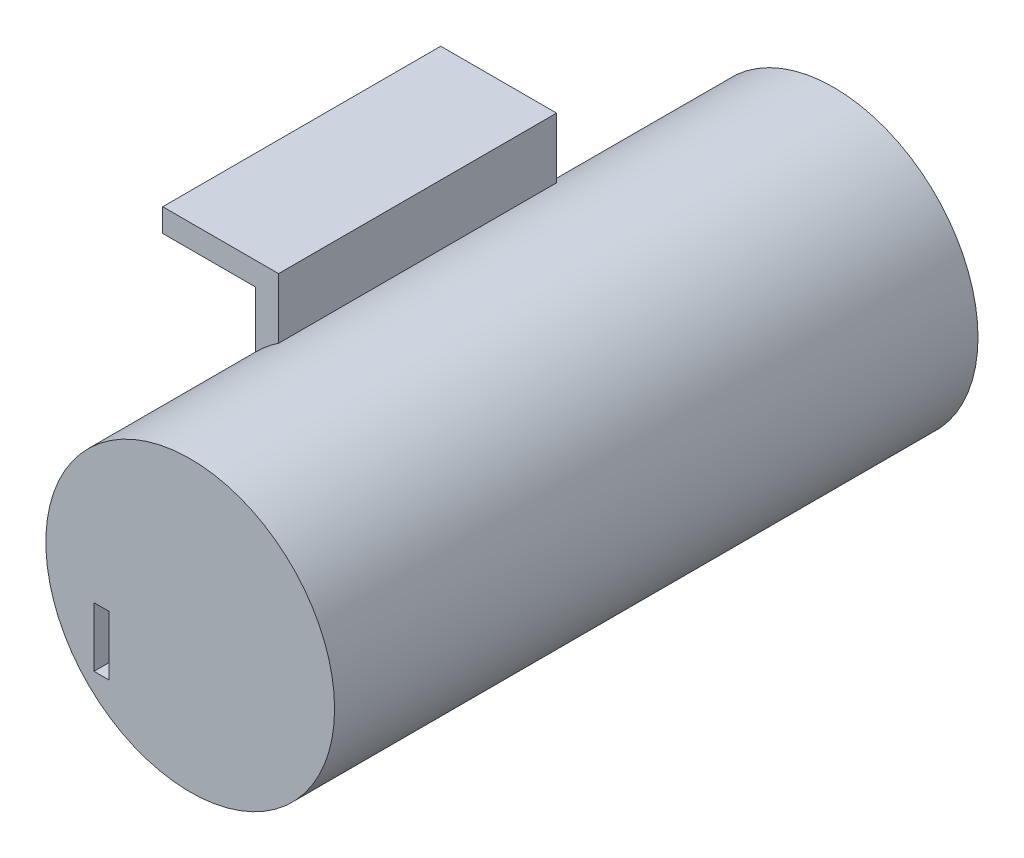
SolidWorks part; units mm, degrees
ref_plane "Front" through (0, 0, 0) normal (0, 0, 1) x (1, 0, 0)
ref_plane "Top" through (0, 0, 0) normal (0, 1, 0) x (1, 0, 0)
ref_plane "Right" through (0, 0, 0) normal (1, 0, 0) x (0, 0, -1)
sketch "Sketch1" plane through (0, 0, 0) normal (0, 0, 1) x (1, 0, 0)
  line L1 (-9.812, 11.8757) -> (-6.637, 11.8757)
  line L2 (-9.812, 11.8757) -> (-9.812, 0.8757)
  line L3 (-9.812, 0.8757) -> (-6.637, 0.8757)
  line L4 (-6.637, 11.8757) -> (-6.637, 0.8757)
  line L5 (-9.812, 8.7007) -> (-22.512, 8.7007)
  line L6 (-9.812, 8.7007) -> (-9.812, 11.8757)
  line L7 (-9.812, 11.8757) -> (-22.512, 11.8757)
  line L8 (-22.512, 8.7007) -> (-22.512, 11.8757)
  dimension "D1" = 11
  dimension "D2" = 3.175
  dimension "D3" = 3.175
  dimension "D4" = 12.7
extrude "Boss-Extrude1" add sketch "Sketch1" along normal blind 38.1 contours L8 L5 L2 L7 | L4 L1 L2 L3 region at (-8.2245, 6.3757, 0) region at (-16.162, 10.2882, 0)
sketch "Sketch2" plane through (0, 0, 0) normal (0, 0, -1) x (-1, 0, 0)
  circle A0 centre (-4.3298, -12.862) radius 19.7846
  circle A1 centre (-4.3298, -12.862) radius 18.4
extrude "Boss-Extrude2" add sketch "Sketch2" against normal blind 58 and the other way blind 27
sketch "Sketch3" plane through (0, 0, 58) normal (0, 0, 1) x (1, 0, 0)
  circle A0 centre (4.3298, -12.862) radius 19.7846
extrude "Boss-Extrude3" add sketch "Sketch3" along normal blind 3.175
sketch "Sketch4" plane through (0, 0, 61.175) normal (0, 0, 1) x (1, 0, 0)
  line L1 (-8.8496, -16.7508) -> (-6.7962, -16.7508)
  line L2 (-8.8496, -16.7508) -> (-8.8496, -24.8958)
  line L3 (-8.8496, -24.8958) -> (-6.7962, -24.8958)
  line L4 (-6.7962, -16.7508) -> (-6.7962, -24.8958)
extrude "Cut-Extrude1" cut sketch "Sketch4" against normal blind 3.175
